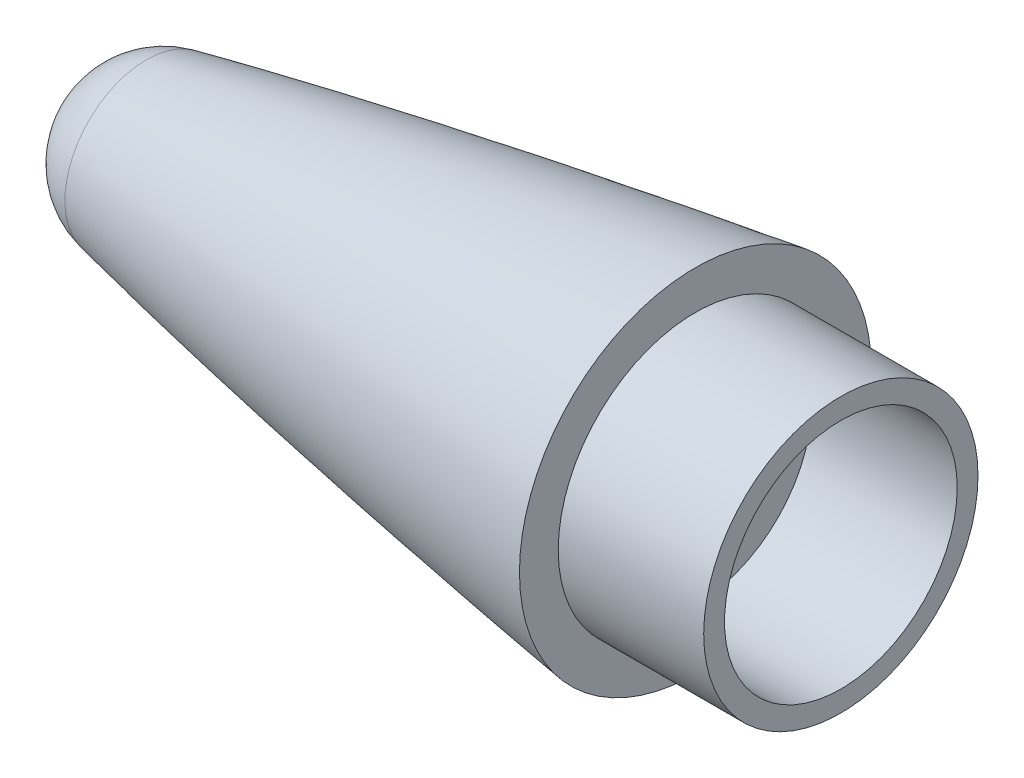
SolidWorks part; units mm, degrees
ref_plane "Front Plane" through (0, 0, 0) normal (0, 0, 1) x (1, 0, 0)
ref_plane "Top Plane" through (0, 0, 0) normal (0, 1, 0) x (1, 0, 0)
ref_plane "Right Plane" through (0, 0, 0) normal (1, 0, 0) x (0, 0, -1)
sketch "Sketch1" plane through (0, 0, 0) normal (0, 0, 1) x (1, 0, 0)
  line L0 (0, 0) -> (600, 0) construction
  line L1 (600, 0) -> (600, 78.36) construction
  line L2 (600, 78.36) -> (650, 78.36)
  line L3 (650, 78.36) -> (650, 55)
  line L4 (650, 55) -> (806.72, 55)
  line L5 (806.72, 55) -> (806.72, 0)
  line L6 (806.72, 0) -> (0, 0)
  line L7 (200, 0) -> (200, 42.3283)
  circle A0 centre (72.0133, 0) radius 20
  spline S0 degree 4 poles (0, 0) (0.0016, 0.0064) (0.0058, 0.0188) (0.0175, 0.0422) (0.0463, 0.0862) (0.0915, 0.1423) (0.1543, 0.2091) (0.2763, 0.3247) (0.4211, 0.4433) (0.5863, 0.5665) (0.8395, 0.741) (1.183, 0.9602) (1.7828, 1.3087) (2.8683, 1.8716) (4.7628, 2.7397) (8.1903, 4.116) (14.423, 6.288) (24.8043, 9.4077) (38.8995, 13.0876) (55.9277, 17.0568) (79.0908, 21.9784) (106.8812, 27.3296) (139.4042, 33.0214) (176.6683, 38.9539) (214.0039, 44.4169) (251.3968, 49.4711) (288.8378, 54.1545) (326.3207, 58.4893) (363.8412, 62.4863) (401.396, 66.1465) (438.983, 69.4606) (476.6007, 72.4071) (509.5423, 74.6287) (537.7965, 76.2335) (560.2923, 77.2755) (575.1954, 77.8326) (587.2142, 78.173) (594.52, 78.3104) (598.1733, 78.3543) (600, 78.36) knots 0 0 0 0 0 0.000043 0.000086 0.000173 0.000345 0.000518 0.00069 0.00128 0.001578 0.001875 0.002717 0.003965 0.006149 0.009932 0.016448 0.028301 0.04964 0.081363 0.112452 0.14354 0.205717 0.267893 0.33007 0.392247 0.454423 0.5166 0.578777 0.640954 0.70313 0.765307 0.827484 0.88966 0.920749 0.951837 0.975919 0.987959 1 1 1 1 1 construction
  spline S1 degree 4 poles (0, 0) (0.0016, 0.0064) (0.0058, 0.0188) (0.0175, 0.0422) (0.0463, 0.0862) (0.0915, 0.1423) (0.1543, 0.2091) (0.2763, 0.3247) (0.4211, 0.4433) (0.5863, 0.5665) (0.8395, 0.741) (1.183, 0.9602) (1.7828, 1.3087) (2.8683, 1.8716) (4.7628, 2.7397) (8.1903, 4.116) (14.423, 6.288) (24.8043, 9.4077) (38.8995, 13.0876) (55.9277, 17.0568) (79.0908, 21.9784) (106.8812, 27.3296) (139.4042, 33.0214) (176.6683, 38.9539) (214.0039, 44.4169) (251.3968, 49.4711) (288.8378, 54.1545) (326.3207, 58.4893) (363.8412, 62.4863) (401.396, 66.1465) (438.983, 69.4606) (476.6007, 72.4071) (509.5423, 74.6287) (537.7965, 76.2335) (560.2923, 77.2755) (575.1954, 77.8326) (587.2142, 78.173) (594.52, 78.3104) (598.1733, 78.3543) (600, 78.36) knots 0 0 0 0 0 0.000043 0.000086 0.000173 0.000345 0.000518 0.00069 0.00128 0.001578 0.001875 0.002717 0.003965 0.006149 0.009932 0.016448 0.028301 0.04964 0.081363 0.112452 0.14354 0.205717 0.267893 0.33007 0.392247 0.454423 0.5166 0.578777 0.640954 0.70313 0.765307 0.827484 0.88966 0.920749 0.951837 0.975919 0.987959 1 1 1 1 1
  dimension "D6" = 40
  dimension "D1" = 78.36
  dimension "D2" = 55
  dimension "D3" = 156.72
  dimension "D4" = 50
  dimension "D5" = 200
revolve "Revolve1" add sketch "Sketch1" angle 360 about L6 region at (148.4577, 17.3032, 0) region at (72.0133, 8.4883, 0)
sketch "Sketch3" plane through (200, 0, 0) normal (1, 0, 0) x (0, 0, -1)
  circle A0 centre (0, 20) radius 3.1
  circle A1 centre (0, -20) radius 3.1
  circle A2 centre (0, 0) radius 20 construction
  circle A3 centre (0, 0) radius 33
  circle A5 centre (0, 0) radius 28
  dimension "D1" = 6.2
  dimension "D2" = 40
  dimension "D3" = 13
  dimension "D4" = 5
extrude "Boss-Extrude1" add sketch "Sketch3" along normal blind 35 contours A3 A5 region at (200, 0, 32.0666)
